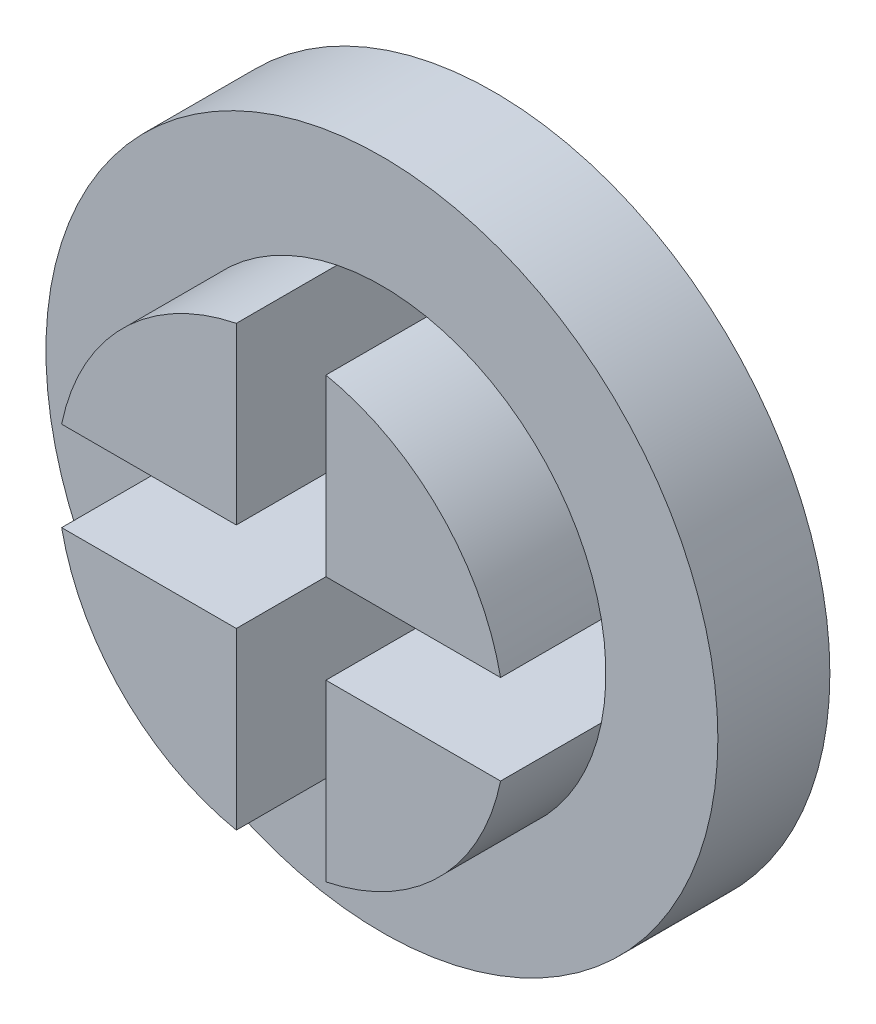
SolidWorks part; units mm, degrees
ref_plane "Front Plane" through (0, 0, 0) normal (0, 0, 1) x (1, 0, 0)
ref_plane "Top Plane" through (0, 0, 0) normal (0, 1, 0) x (1, 0, 0)
ref_plane "Right Plane" through (0, 0, 0) normal (1, 0, 0) x (0, 0, -1)
sketch "Sketch1" plane through (0, 0, 0) normal (0, 0, 1) x (1, 0, 0)
  line L2 (-2, -9.798) -> (-2, 9.798)
  line L4 (2, -9.798) -> (2, 9.798)
  line L5 (-1.5542, -9.8785) -> (1.5542, 9.8785) construction
  line L6 (-1.5542, 9.8785) -> (1.5542, -9.8785) construction
  line L7 (-9.798, 2) -> (9.798, 2)
  line L9 (-9.798, -2) -> (9.798, -2)
  line L11 (-9.885, 1.5125) -> (9.885, -1.5125) construction
  line L12 (-9.885, -1.5125) -> (9.885, 1.5125) construction
  circle A0 centre (0, 0) radius 10
  circle A1 centre (0, 0) radius 15
  dimension "D1" = 20
  dimension "D2" = 30
extrude "Boss-Extrude1" add sketch "Sketch1" along normal blind 5 contours A1 A0 L4 region at (-14.5757, 0, 0)
extrude "Boss-Extrude2" add sketch "Sketch1<3>" along normal blind 9.5 contours L2 A0 L7 | L7 A0 L4 | L4 A0 L9 | L9 A0 L2 region at (-5.1128, -5.1128, 0) region at (5.1128, -5.1128, 0) region at (-5.1128, 5.1128, 0) region at (5.1128, 5.1128, 0)
sketch "Sketch1<3>" plane through (0, 0, 0) normal (0, 0, 1) x (1, 0, 0) same geometry as "Sketch1"
fillet "Fillet1" radius 0.5 12 edges at (2, 5.899, 0) (5.899, 2, 0) (10, 0, 0) (5.899, -2, 0) (0, -10, 0) (2, -5.899, 0) (-2, -5.899, 0) (-5.899, -2, 0) (-10, 0, 0) (-5.899, 2, 0) (0, 10, 0) (-2, 5.899, 0)
